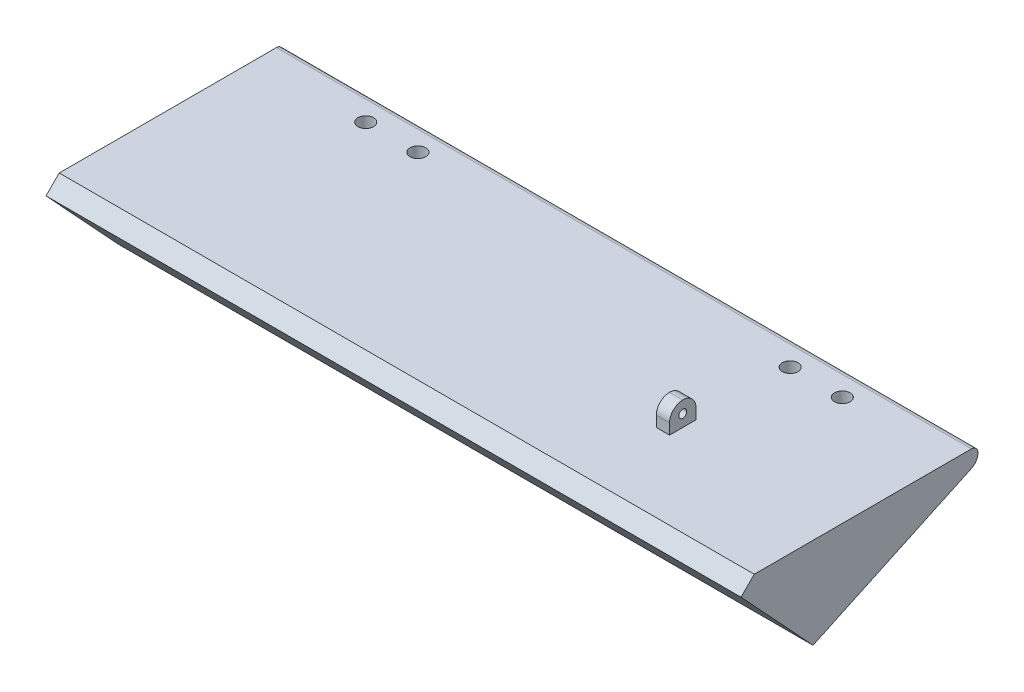
SolidWorks part; units mm, degrees
ref_plane "Front Plane" through (0, 0, 0) normal (0, 0, 1) x (1, 0, 0)
ref_plane "Top Plane" through (0, 0, 0) normal (0, 1, 0) x (1, 0, 0)
ref_plane "Right Plane" through (0, 0, 0) normal (1, 0, 0) x (0, 0, -1)
sketch "Sketch1" plane through (0, 0, 0) normal (0, 1, 0) x (1, 0, 0)
  line L1 (0, 0) -> (133.35, 0)
  line L2 (0, 0) -> (0, -45.466)
  line L3 (0, -45.466) -> (133.35, -45.466)
  line L4 (133.35, 0) -> (133.35, -45.466)
  dimension "D1" = 133.35
  dimension "D2" = 45.466
extrude "Boss-Extrude1" add sketch "Sketch1" along normal blind 2.54
sketch "Sketch2" plane through (133.35, 0, 0) normal (1, 0, 0) x (0, 0, -1)
  line L0 (-45.466, 2.54) -> (-45.466, 0) construction
  line L2 (-45.466, 0) -> (-45.466, 2.54)
  line L3 (-45.466, 2.54) -> (-42.926, 2.54)
  line L5 (-45.466, 2.54) -> (0, 2.54) construction
  line L6 (-42.926, 2.54) -> (-45.466, 0)
  dimension "D2" = 45
extrude "Cut-Extrude1" cut sketch "Sketch2" against normal through all
sketch "Sketch4" plane through (0, 2.54, 0) normal (0, 1, 0) x (1, 0, 0)
  line L0 (133.35, 0) -> (0, 0) construction
  line L1 (102.108, -27.94) -> (99.568, -27.94)
  line L2 (102.108, -27.94) -> (102.108, -22.86)
  line L3 (102.108, -22.86) -> (99.568, -22.86)
  line L4 (99.568, -27.94) -> (99.568, -22.86)
  line L9 (133.35, -42.926) -> (133.35, 0) construction
  dimension "D1" = 2.54
  dimension "D2" = 5.08
  dimension "D3" = 22.86
  dimension "D4" = 31.242
extrude "Boss-Extrude2" add sketch "Sketch4" along normal blind 4.572
sketch "Sketch5" plane through (102.108, 0, 0) normal (1, 0, 0) x (0, 0, -1)
  line L0 (-25.4, 2.54) -> (-25.4, 7.112) construction
  line L1 (-27.94, 2.54) -> (-22.86, 2.54) construction
  line L2 (-27.94, 7.112) -> (-22.86, 7.112) construction
  circle A0 centre (-25.4, 4.826) radius 0.762
  dimension "D1" = 1.524
extrude "Cut-Extrude2" cut sketch "Sketch5" against normal through all
fillet "Fillet1" radius 2.54 1 edges at (100.838, 7.112, 27.94)
fillet "Fillet2" radius 2.54 1 edges at (100.838, 7.112, 22.86)
fillet "Fillet3" radius 1.27 2 edges at (66.675, 0, 0) (66.675, 2.54, 0)
sketch "Sketch8" plane through (0, 0, 0) normal (-1, 0, 0) x (0, 0, 1)
  line L1 (31.6525, -14.9027) -> (1.27, -0.7242)
  line L5 (1.27, 2.54) -> (42.926, 2.54) construction
  line L7 (1.27, 2.54) -> (15.5607, 2.54)
  line L8 (1.27, 0) -> (1.27, -0.7242) construction
  line L9 (45.466, 0) -> (1.27, 0)
  line L10 (1.27, 0) -> (45.466, 0) construction
  line L11 (45.466, 0) -> (1.27, 0)
  line L12 (31.6525, -14.9027) -> (45.466, 0)
  arc A0 (1.27, -0.7242) -> (0, 1.27) centre (2.2006, 1.27) cw
  arc A1 (1.27, 0) -> (0, 1.27) centre (1.27, 1.27) cw
  arc A2 (0, 1.27) -> (1.27, 0) centre (1.27, 1.27) ccw construction
  point P21 (0.372, 0.372)
  arc M7 (0, 1.27) -> (1.27, 0) centre (1.27, 1.27) ccw
  line M8 (1.27, 0) -> (45.466, 0)
  dimension "D1" = 33.528
  dimension "D2" = 20.32
extrude "Boss-Extrude4" add sketch "Sketch8" against normal blind 133.35 contours L1 L12 M8 | L8 A0 M7 region at (0, -4.9754, 25.6533) region at (0, -0.0907, 0.7833)
sketch "Sketch10" plane through (0, 2.54, 0.5076) normal (0, -1, 0) x (1, 0, 0)
  line L0 (0, 4.5724) -> (20.955, 4.5724) construction
  line L2 (20.955, 4.5724) -> (30.9626, 4.5724) construction
  line L3 (133.35, 4.5724) -> (112.395, 4.5724) construction
  line L5 (112.395, 4.5724) -> (102.3874, 4.5724) construction
  line L6 (133.35, 31.1449) -> (133.35, 0.7624) construction
  line L10 (0, 31.1449) -> (0, 0.7624) construction
  line L12 (133.35, -0.5076) -> (0, -0.5076) construction
  circle A0 centre (20.955, 4.5724) radius 1.4986
  circle A1 centre (30.9626, 4.5724) radius 1.4986
  circle A2 centre (102.3874, 4.5724) radius 1.4986
  circle A3 centre (112.395, 4.5724) radius 1.4986
  dimension "D4" = 2.9972
  dimension "D5" = 2.9972
  dimension "D6" = 2.9972
  dimension "D7" = 2.9972
  dimension "D1" = 20.955
  dimension "D2" = 10.0076
  dimension "D3" = 5.08
extrude "Cut-Extrude3" cut sketch "Sketch10" along normal blind 2.54
